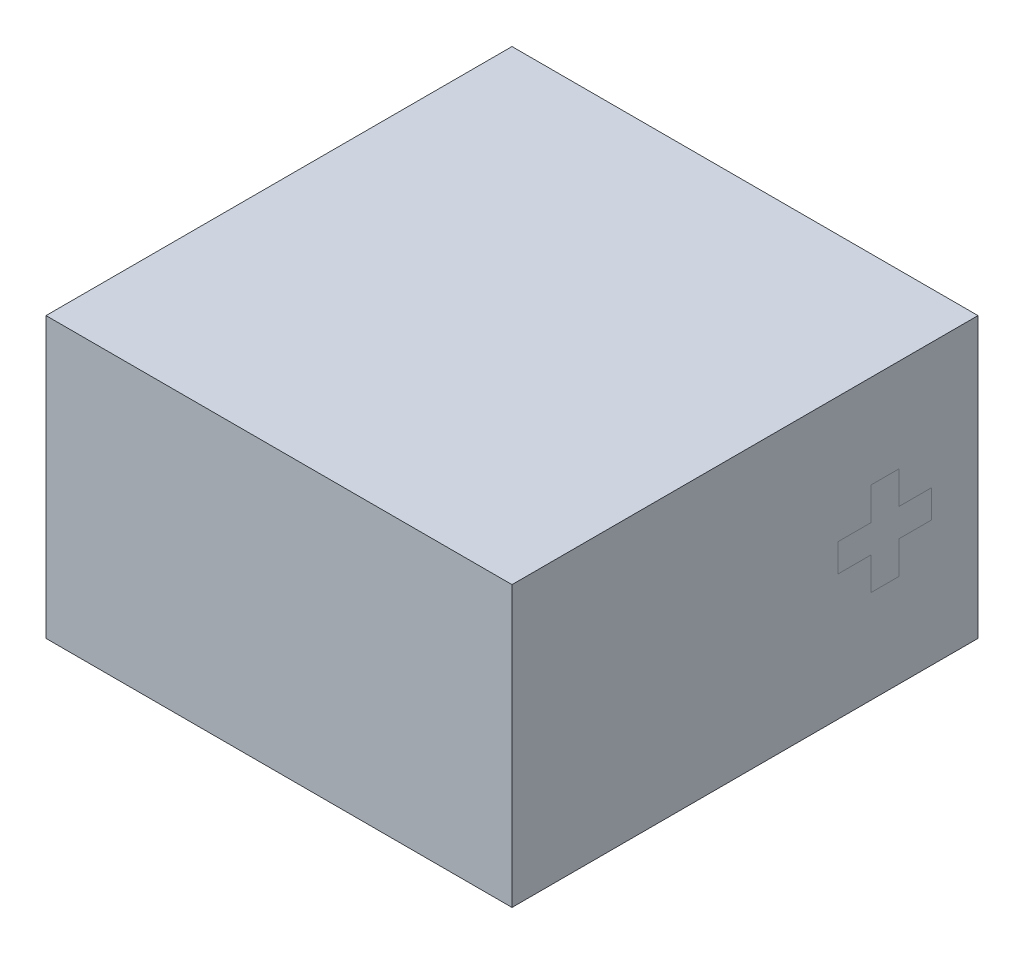
SolidWorks part; units mm, degrees
ref_plane "Front Plane" through (0, 0, 0) normal (0, 0, 1) x (1, 0, 0)
ref_plane "Top Plane" through (0, 0, 0) normal (0, 1, 0) x (1, 0, 0)
ref_plane "Right Plane" through (0, 0, 0) normal (1, 0, 0) x (0, 0, -1)
sketch "Sketch1" plane through (0, 0, 0) normal (0, 1, 0) x (1, 0, 0)
  line L0 (0, 0) -> (18.6879, 0) construction
  line L1 (0, 0) -> (0, -14.4281) construction
  line L3 (-2.5, 2.5) -> (2.5, 2.5)
  line L4 (-2.5, 2.5) -> (-2.5, -2.5)
  line L5 (-2.5, -2.5) -> (2.5, -2.5)
  line L6 (2.5, 2.5) -> (2.5, -2.5)
  dimension "D1" = 5
extrude "Boss-Extrude1" add sketch "Sketch1" along normal blind 3
sketch "Sketch2" plane through (2.5, 0, 0) normal (1, 0, 0) x (0, 0, -1)
  line L0 (-2.5, 1.5) -> (2.5, 1.5) construction
  line L1 (-2.5, 3) -> (-2.5, 0) construction
  line L2 (2.5, 3) -> (2.5, 0) construction
  line L3 (1.5, 3) -> (1.5, 0) construction
  line L4 (1.35, 2) -> (1.65, 2)
  line L6 (-2.5, 3) -> (2.5, 3) construction
  line L7 (-2.5, 0) -> (2.5, 0) construction
  line L8 (1.35, 2) -> (1.35, 1.65)
  line L9 (1.35, 1) -> (1.65, 1)
  line L10 (1.65, 2) -> (1.65, 1.65)
  line L11 (1.35, 2) -> (1.65, 1) construction
  line L12 (1.35, 1) -> (1.65, 2) construction
  line L13 (1, 1.65) -> (1.35, 1.65)
  line L14 (1, 1.65) -> (1, 1.35)
  line L15 (1, 1.35) -> (1.35, 1.35)
  line L16 (2, 1.65) -> (2, 1.35)
  line L17 (1, 1.65) -> (2, 1.35) construction
  line L18 (1, 1.35) -> (2, 1.65) construction
  line L19 (1.35, 1.35) -> (1.35, 1)
  line L21 (1.65, 1.65) -> (2, 1.65)
  line L22 (1.65, 1.35) -> (2, 1.35)
  line L23 (1.65, 1.35) -> (1.65, 1)
  point P12 (1.5, 1.5)
  point P13 (1.5, 1.5)
  point P18 (1.5, 1.5)
  dimension "D1" = 1
  dimension "D2" = 0.3
  dimension "D4" = 1
  dimension "D5" = 0.3
wrap "Wrap1" sketch "Sketch2" wrap type scribe source sketch "Sketch2" face at (2.5, 1.5, 0)
